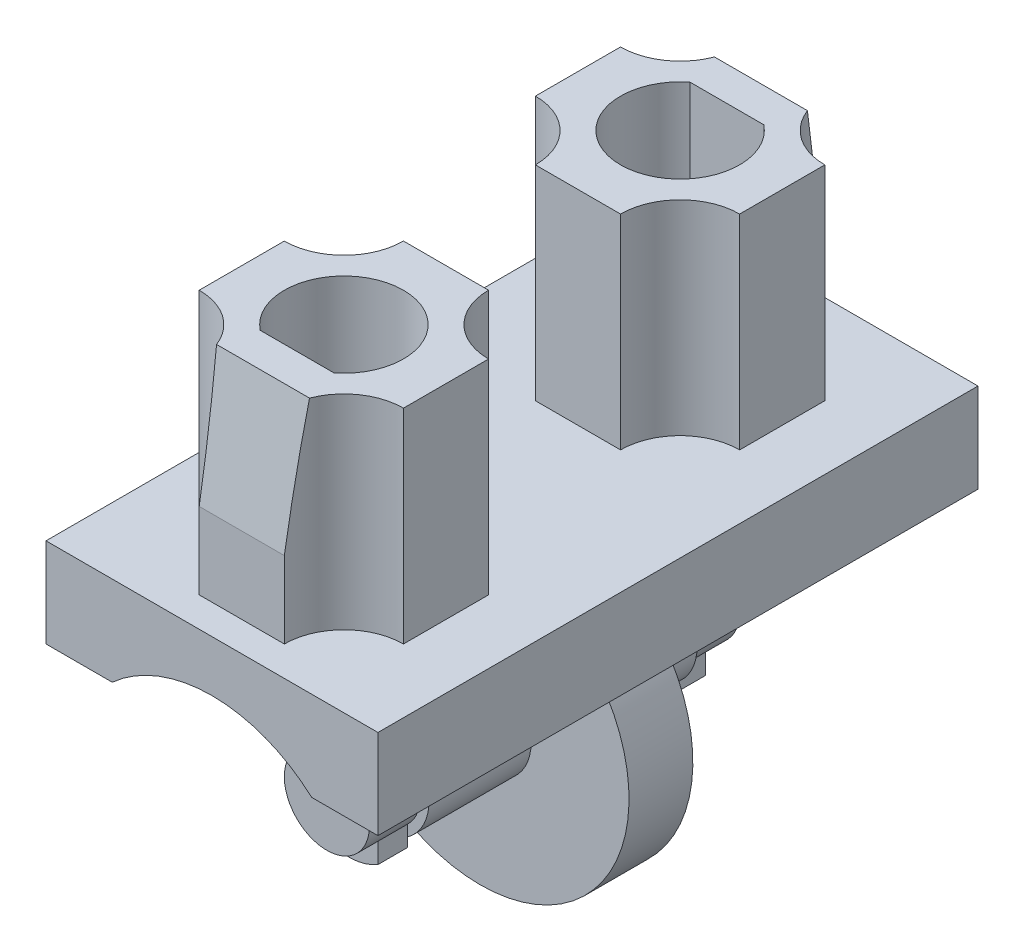
SolidWorks part; units mm, degrees
ref_plane "Front Plane" through (0, 0, 0) normal (0, 0, 1) x (1, 0, 0)
ref_plane "Top Plane" through (0, 0, 0) normal (0, 1, 0) x (1, 0, 0)
ref_plane "Right Plane" through (0, 0, 0) normal (1, 0, 0) x (0, 0, -1)
sketch "Sketch1" plane through (0, 0, 0) normal (0, 0, 1) x (1, 0, 0)
  line L0 (2.3431, 2.6) -> (3.9, 2.6)
  line L1 (-3.9, 4.7) -> (3.9, 4.7)
  line L2 (-3.9, 4.7) -> (-3.9, 2.6)
  line L3 (-3.9, 2.6) -> (-2.3431, 2.6)
  line L4 (3.9, 4.7) -> (3.9, 2.6)
  line L5 (-3.9, 4.7) -> (3.9, 2.6) construction
  line L6 (-3.9, 2.6) -> (3.9, 4.7) construction
  circle A0 centre (0, 0) radius 3.5
  point P3 (0, 3.65)
  point P8 (0, 0)
  dimension "D1" = 7
  dimension "D2" = 2.1
  dimension "D3" = 7.8
  dimension "D4" = 4.7
extrude "Hip Base" add sketch "Sketch1" along normal mid plane 14.1 contours A0 L0 L4 L1 L2 L3 region at (0, 3.7971, 0)
extrude "Leg Joint" add sketch "Sketch1<3>" along normal mid plane 1.5 contours A0 region at (0, 0, 0)
sketch "Sketch1<3>" plane through (0, 0, 0) normal (0, 0, 1) x (1, 0, 0) same geometry as "Sketch1"
sketch "Sketch2" plane through (0, 0, 0.75) normal (0, 0, 1) x (1, 0, 0)
  circle A0 centre (0, 0) radius 1.2
  dimension "D1" = 2.4
extrude "Leg Peg" add sketch "Sketch2" along normal blind 2.4
sketch "Sketch3" plane through (0, 0, 3.15) normal (0, 0, 1) x (1, 0, 0)
  line L0 (-0.6614, 0.75) -> (0.6614, 0.75)
  arc A0 (-0.6614, 0.75) -> (0.6614, 0.75) centre (0, 0) ccw
  dimension "D1" = 2
  dimension "D2" = 0.75
extrude "Leg Peg Inner" add sketch "Sketch3" along normal blind 1.2
sketch "Sketch4" plane through (0, 0, 3.15) normal (0, 0, 1) x (1, 0, 0)
  line L2 (-0.7, -0.7141) -> (-0.7, -1.1893)
  line L4 (0.7, -0.7141) -> (0.7, -1.1893)
  arc A2 (-0.7, -1.1893) -> (0.7, -1.1893) centre (0, 0) ccw
  arc A3 (-0.7, -0.7141) -> (0.7, -0.7141) centre (0, 0) ccw
  point P6 (0, -1)
  dimension "D2" = 1.4
  dimension "D3" = 0.7
extrude "Boss-Extrude5" add sketch "Sketch4" along normal blind 0.7
sketch "Sketch7" plane through (0, 4.7, 0) normal (0, 1, 0) x (1, 0, 0)
  line L0 (0, 0) -> (0, -7.05) construction
  line L1 (-3.9, -7.05) -> (3.9, -7.05) construction
  line L3 (-2.4, -1.55) -> (2.4, -1.55)
  line L4 (-2.4, -1.55) -> (-2.4, -6.35)
  line L5 (-2.4, -6.35) -> (2.4, -6.35)
  line L6 (2.4, -1.55) -> (2.4, -6.35)
  line L7 (-2.4, -1.55) -> (2.4, -6.35) construction
  line L8 (-2.4, -6.35) -> (2.4, -1.55) construction
  circle A0 centre (2.4, -1.55) radius 1.4
  circle A1 centre (2.4, -6.35) radius 1.4
  circle A2 centre (-2.4, -6.35) radius 1.4
  circle A3 centre (-2.4, -1.55) radius 1.4
  point P5 (0, -3.95)
  point P20 (0, -3.95)
  dimension "D4" = 2.8
  dimension "D1" = 1.55
  dimension "D2" = 4.8
  dimension "D3" = 4.8
  dimension "D5" = 4
extrude "Hip Peg" add sketch "Sketch7" along normal blind 4.8 contours A3 L4 A2 L5 A1 L6 A0 L3 region at (0, 4.7, 3.95)
sketch "Sketch8" plane through (0, 9.5, 0) normal (0, 1, 0) x (1, 0, 0)
  line L0 (1, -6.35) -> (-1, -1.55) construction
  line L1 (-1, -6.35) -> (1, -6.35) construction
  line L2 (-0.866, -5.05) -> (0.866, -5.05)
  arc A0 (2.4, -4.95) -> (1, -6.35) centre (2.4, -6.35) ccw construction
  arc A1 (0.866, -5.05) -> (-0.866, -5.05) centre (0, -3.95) ccw
  dimension "D1" = 2.8
  dimension "D2" = 1.3
extrude "Hip Cavity" cut sketch "Sketch8" against normal up to surface (4.8 mm away) up to face at (0, 4.7, 3.95)
sketch "Sketch9" plane through (0, 0, 0) normal (1, 0, 0) x (0, 0, -1)
  line L0 (-6.35, 9.5) -> (-5.85, 9.5)
  line L1 (-4.95, 9.5) -> (-6.35, 9.5) construction
  line L2 (-5.85, 9.5) -> (-6.35, 6.5)
  line L3 (-6.35, 9.5) -> (-6.35, 4.7) construction
  line L4 (-6.35, 6.5) -> (-6.35, 9.5)
  dimension "D1" = 0.5
  dimension "D2" = 3
extrude "Hip Peg Chamfer" cut sketch "Sketch9" against normal through all both and the other way through all
mirror "Mirror1" about plane through (0, 0, 0) normal (0, 0, 1) of "Hip Peg Chamfer", "Hip Cavity", "Hip Peg", "Boss-Extrude5", "Leg Peg Inner", "Leg Peg"
